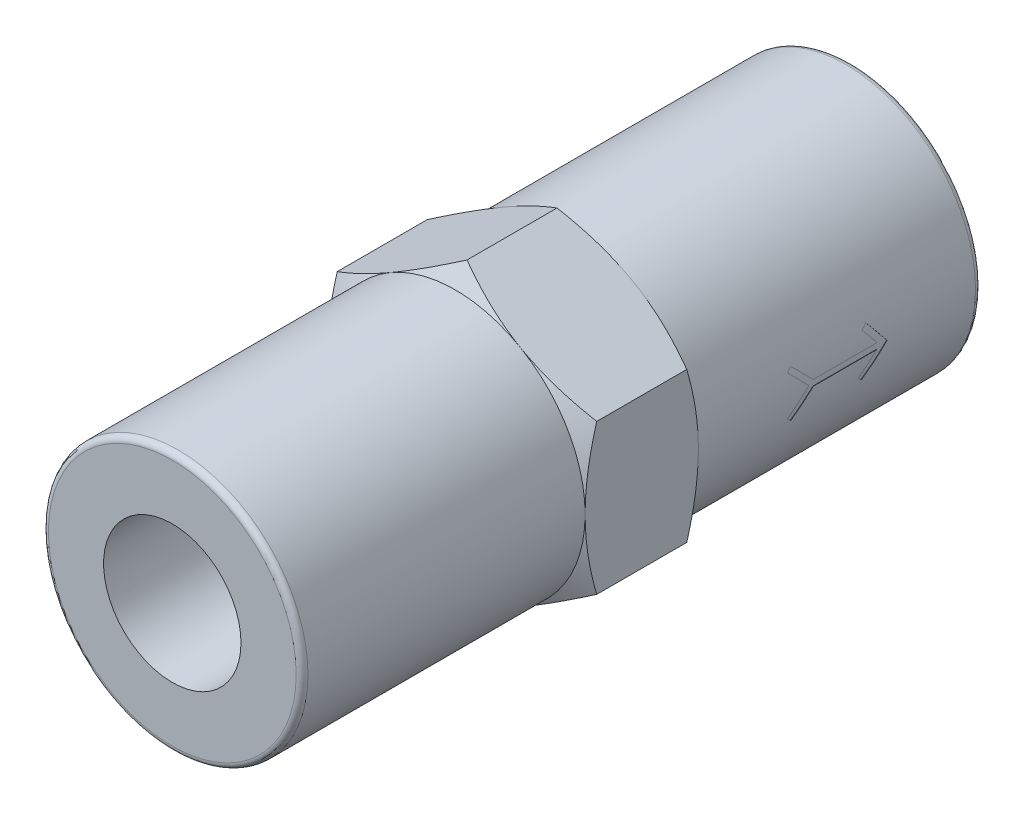
SolidWorks part; units mm, degrees
ref_plane "Front Plane" through (0, 0, 0) normal (0, 0, 1) x (1, 0, 0)
ref_plane "Top Plane" through (0, 0, 0) normal (0, 1, 0) x (1, 0, 0)
ref_plane "Right Plane" through (0, 0, 0) normal (1, 0, 0) x (0, 0, -1)
sketch "Sketch1" plane through (0, 0, 0) normal (1, 0, 0) x (0, 0, -1)
  line L0 (-22.86, 0) -> (22.86, 0) construction
  line L1 (-3.81, 0) -> (3.81, 0) construction
  line L2 (0, 8.7312) -> (0, -8.7312) construction
  line L3 (-22.86, 6.858) -> (-22.86, -6.858) construction
  line L4 (-22.86, 6.858) -> (-12.6543, 6.5402) construction
  line L5 (-12.6543, 6.5402) -> (-12.6543, 0) construction
  line L6 (22.86, 6.858) -> (22.86, -6.858) construction
  line L7 (22.86, 6.858) -> (12.6543, 6.5402) construction
  line L8 (12.6543, 6.5402) -> (12.6543, 0) construction
  line L9 (0, 4.6228) -> (0, -4.6228) construction
  point P17 (-22.86, 8.7312)
  point P18 (22.86, 8.7312)
  dimension "A1" = 1.783
  dimension "A2" = 1.783
sketch "Sketch1.1" plane through (0, 0, 0) normal (0, 0, 1) x (1, 0, 0)
  line L1 (0, 10.082) -> (-8.7312, 5.041)
  line L2 (-8.7312, 5.041) -> (-8.7313, -5.041)
  line L3 (-8.7313, -5.041) -> (0, -10.082)
  line L4 (0, -10.082) -> (8.7312, -5.041)
  line L5 (8.7312, -5.041) -> (8.7312, 5.041)
  line L6 (8.7312, 5.041) -> (0, 10.082)
  circle A0 centre (0, 0) radius 8.7312 construction
extrude "Extrude1" add sketch "Sketch1.1" along normal up to vertex (22.86 mm away) and the other way up to vertex (22.86 mm away) up to point (0, 0, 22.86) other way up to point (0, 0, -22.86)
ref_axis "Axis1" through (0, 0, -31.4325) along (0, 0, 1)
sketch "Sketch2.0" [suppressed] plane through (0, 0, 0) normal (0, 0, 1) x (1, 0, 0)
  circle A0 centre (0, 0) radius 12.7 construction
  circle A1 centre (0, 0) radius 12.7
extrude "Extrude2.0" [suppressed] cut sketch "Sketch2.0" along normal up to vertex and the other way up to vertex flip side to cut
sketch "Sketch2.1" [suppressed] plane through (0, 0, 32.385) normal (0, 0, 1) x (1, 0, 0)
  circle A0 centre (0, 0) radius 12.7 construction
  circle A1 centre (0, 0) radius 12.7
extrude "Extrude2.1" [suppressed] cut sketch "Sketch2.1" against normal through all draft 60 flip side to cut
sketch "Sketch2.2" [suppressed] plane through (0, 0, 6.985) normal (0, 0, -1) x (-1, 0, 0)
  circle A0 centre (0, 0) radius 12.7 construction
  circle A1 centre (0, 0) radius 12.7
extrude "Extrude2.2" [suppressed] cut sketch "Sketch2.2" against normal through all draft 60 flip side to cut
sketch "Sketch2.3" [suppressed] plane through (0, 0, -6.985) normal (0, 0, 1) x (1, 0, 0)
  circle A0 centre (0, 0) radius 12.7 construction
  circle A1 centre (0, 0) radius 12.7
extrude "Extrude2.3" [suppressed] cut sketch "Sketch2.3" against normal through all draft 60 flip side to cut
sketch "Sketch2.4" [suppressed] plane through (0, 0, -32.385) normal (0, 0, -1) x (-1, 0, 0)
  circle A0 centre (0, 0) radius 12.7 construction
  circle A1 centre (0, 0) radius 12.7
extrude "Extrude2.4" [suppressed] cut sketch "Sketch2.4" against normal through all draft 60 flip side to cut
sketch "Sketch2.5" [suppressed] plane through (0, 0, 0) normal (1, 0, 0) x (0, 0, -1)
  line L0 (-3.8678, 0) -> (5.715, 0) construction
  line L1 (5.715, 0) -> (2.8575, 2.8575)
  line L2 (-3.8678, 0) -> (-5.715, 0) construction
  line L3 (-5.715, 2.8575) -> (-3.2147, 0.3572)
  line L4 (-5.715, 2.8575) -> (-5.715, -2.8575) construction
  line L5 (2.8575, -2.8575) -> (5.715, 0)
  line L6 (-3.2147, -0.3572) -> (-5.715, -2.8575)
  line L7 (-5.715, -2.8575) -> (2.8575, -2.8575) construction
  line L8 (2.8575, -2.8575) -> (2.8575, 2.8575) construction
  line L9 (2.8575, 2.8575) -> (-5.715, 2.8575) construction
  line L10 (-6.985, 0) -> (-5.715, 0) construction
  line L12 (5.715, 0) -> (6.985, 0) construction
  line L14 (-5.715, 2.8575) -> (-6.2201, 2.3524)
  line L15 (-6.2201, 2.3524) -> (-3.8678, 0)
  line L16 (-5.715, -2.8575) -> (-6.2201, -2.3524)
  line L17 (-6.2201, -2.3524) -> (-3.8678, 0)
  line L18 (-3.2147, 0.3572) -> (4.3475, 0.3572)
  line L19 (-6.2201, 2.3524) -> (2.3524, 2.3524) construction
  line L20 (4.3475, -0.3572) -> (-3.2147, -0.3572)
  line L21 (2.8575, 2.8575) -> (2.3524, 2.3524)
  line L22 (2.3524, 2.3524) -> (4.3475, 0.3572)
  line L23 (-6.2201, -2.3524) -> (2.3524, -2.3524) construction
  line L24 (2.8575, -2.8575) -> (2.3524, -2.3524)
  line L25 (2.3524, -2.3524) -> (4.3475, -0.3572)
  line L26 (0.5664, 0.3572) -> (0.5664, -0.3572) construction
  line L27 (0.5664, 0) -> (0, 0) construction
  dimension "D1" = 0.7144
  dimension "D2" = 5.715
  dimension "D3" = 11.43
  dimension "D4" = 1.27
extrude "Extrude2.5" [suppressed] cut sketch "Sketch2.5" against normal blind 0.0254 from surface
pattern_circular "CirPattern1" [suppressed] count 2 over 360 about axis through (0, 0, -31.4325) along (0, 0, 1) of bodies 117
sketch "Sketch3.1" plane through (0, 0, 0) normal (0, 0, 1) x (1, 0, 0)
  circle A0 centre (0, 0) radius 8.7312
extrude "Extrude3.0" cut sketch "Sketch3.1" along normal up to vertex (22.86 mm away) from vertex flip side to cut up to point (0, 0, 22.86) starting at point (0, 0, 3.81)
extrude "Extrude3.1" cut sketch "Sketch3.1<2>" against normal up to vertex (22.86 mm away) from vertex flip side to cut up to point (0, 0, -22.86) starting at point (0, 0, -3.81)
sketch "Sketch3.1<2>" plane through (0, 0, 0) normal (0, 0, 1) x (1, 0, 0) same geometry as "Sketch3.1"
sketch "Sketch3.2" plane through (0, 0, 3.81) normal (0, 0, 1) x (1, 0, 0)
  circle A0 centre (0, 0) radius 8.7312 construction
  circle A1 centre (0, 0) radius 8.7312
extrude "Extrude3.2" cut sketch "Sketch3.2" against normal through all draft 60 flip side to cut
sketch "Sketch3.3" plane through (0, 0, -3.81) normal (0, 0, -1) x (-1, 0, 0)
  circle A0 centre (0, 0) radius 8.7312 construction
  circle A1 centre (0, 0) radius 8.7312
extrude "Extrude3.3" cut sketch "Sketch3.3" against normal through all draft 60 flip side to cut
fillet "Fillet1" radius 0.3969 2 edges at (8.7312, 0, -22.86) (8.7312, 0, 22.86)
sketch "Sketch3.4" plane through (0, 0, 0) normal (1, 0, 0) x (0, 0, -1)
  line L0 (10.16, 0) -> (16.51, 0) construction
  line L1 (3.81, 0) -> (10.16, 0) construction
  line L2 (16.51, 0) -> (22.86, 0) construction
  line L3 (22.86, -8.3344) -> (22.86, 8.3344) construction
  line L4 (10.16, 1.5875) -> (10.16, -1.5875) construction
  line L5 (10.16, -1.5875) -> (16.51, -1.5875) construction
  line L6 (16.51, -1.5875) -> (16.51, 1.5875) construction
  line L7 (16.51, 1.5875) -> (10.16, 1.5875) construction
  line L8 (10.16, 1.5875) -> (11.5491, 0.1984)
  line L9 (11.5491, -0.1984) -> (10.16, -1.5875)
  line L10 (10.16, -1.5875) -> (9.9111, -1.3386)
  line L11 (9.9111, -1.3386) -> (11.2497, 0)
  line L12 (11.2497, 0) -> (9.9111, 1.3386)
  line L13 (9.9111, 1.3386) -> (10.16, 1.5875)
  line L14 (15.2316, 1.5875) -> (14.9225, 1.3386)
  line L15 (14.9225, 1.3386) -> (9.9111, 1.3386) construction
  line L16 (9.9111, 1.3386) -> (9.9111, -1.3386) construction
  line L17 (9.9111, -1.3386) -> (14.6736, -1.3386) construction
  line L18 (14.9225, -1.5875) -> (14.9225, 1.3386) construction
  line L19 (14.9225, 1.3386) -> (15.8406, 0.1984)
  line L20 (15.2316, 1.5875) -> (16.51, 0)
  line L21 (16.51, 0) -> (14.9225, -1.5875)
  line L22 (14.9225, -1.5875) -> (14.6736, -1.3386)
  line L23 (14.6736, -1.3386) -> (15.8137, -0.1984)
  line L24 (11.5491, 0.1984) -> (15.8406, 0.1984)
  line L25 (11.5491, -0.1984) -> (15.8137, -0.1984)
  line L28 (13.335, -0.1984) -> (13.335, 0.1984) construction
  point P28 (13.335, 0)
  dimension "D2" = 0.3969
  dimension "D3" = 3.175
  dimension "D1" = 6.35
extrude "Extrude3.4" cut sketch "Sketch3.4" against normal blind 0.0254 from surface starting at face at (8.7312, 0, -22.4631)
pattern_circular "CirPattern3" count 2 over 360 about axis through (0, 0, -31.4325) along (0, 0, 1) of "Extrude3.4"
sketch "Sketch4" plane through (0, 0, 0) normal (0, 0, 1) x (1, 0, 0)
  circle A0 centre (0, 0) radius 4.6228
extrude "Extrude4" cut sketch "Sketch4" against normal through all and the other way through all
sketch "Sketch5" plane through (0, 0, 0) normal (0, 0, 1) x (1, 0, 0)
  circle A1 centre (0, 0) radius 4.6228 construction
  circle A2 centre (0, 0) radius 4.6228
extrude "Extrude5" add sketch "Sketch5" along normal up to vertex (3.81 mm away) and the other way up to vertex (3.81 mm away) up to point (0, 0, 3.81) other way up to point (0, 0, -3.81)
sketch "Sketch7" [suppressed] plane through (0, 0, 22.86) normal (0, 0, 1) x (1, 0, 0)
  circle A0 centre (0, 0) radius 6.858
extrude "Extrude7" [suppressed] cut sketch "Sketch7" against normal up to vertex draft 1.783
sketch "Sketch8" [suppressed] plane through (0, 0, 12.6543) normal (0, 0, 1) x (1, 0, 0)
  circle A0 centre (0, 0) radius 6.5402 construction
  circle A1 centre (0, 0) radius 6.5402
curve "Helix/Spiral1" [suppressed] parameters "Pitch 1"=1.4111
sketch "Sketch9" [suppressed] plane through (0, 0, 0) normal (1, 0, 0) x (0, 0, -1)
  line L0 (-12.0369, 6.5402) -> (-12.0369, 5.6237) construction
  line L1 (-12.7425, 6.693) -> (-11.3314, 6.693) construction
  line L2 (-11.3314, 6.693) -> (-12.0369, 5.4709) construction
  line L3 (-12.0369, 5.4709) -> (-12.7425, 6.693) construction
  line L4 (-12.6543, 6.5402) -> (-11.4196, 6.5402) construction
  line L5 (-12.0369, 6.5402) -> (-12.0369, 6.693) construction
  line L6 (-12.0369, 5.6237) -> (-12.0369, 5.4709) construction
  line L7 (-11.4196, 6.5402) -> (-11.9487, 5.6237)
  line L8 (-11.9487, 5.6237) -> (-12.1251, 5.6237)
  line L9 (-12.1251, 5.6237) -> (-12.7425, 6.693)
  line L12 (-12.7425, 6.693) -> (-11.4196, 6.5402)
  dimension "D1" = 0.1764
sweep "Sweep1" [suppressed] add profiles "Sketch9" path "Helix/Spiral1"
sketch "Sketch10" [suppressed] plane through (0, 0, 22.86) normal (0, 0, 1) x (1, 0, 0)
  circle A0 centre (0, 0) radius 6.858 construction
  circle A1 centre (0, 0) radius 6.858 construction
  circle A2 centre (0, 0) radius 7.2108
  dimension "D1" = 0.3528
extrude "Extrude8" [suppressed] cut sketch "Sketch10" against normal through all draft 45 and the other way through all draft 45
sketch "Sketch11" [suppressed] plane through (0, 0, -22.86) normal (0, 0, -1) x (-1, 0, 0)
  circle A0 centre (0, 0) radius 6.858
extrude "Extrude9" [suppressed] cut sketch "Sketch11" against normal up to vertex draft 1.783
sketch "Sketch12" [suppressed] plane through (0, 0, -12.6543) normal (0, 0, -1) x (-1, 0, 0)
  circle A0 centre (0, 0) radius 6.5402 construction
  circle A1 centre (0, 0) radius 6.5402
curve "Helix/Spiral2" [suppressed] parameters "Pitch 2"=1.4111
sketch "Sketch13" [suppressed] plane through (0, 0, 0) normal (1, 0, 0) x (0, 0, -1)
  line L0 (11.3314, 6.693) -> (12.0369, 5.4709) construction
  line L1 (12.0369, 5.4709) -> (12.7425, 6.693) construction
  line L2 (12.7425, 6.693) -> (11.3314, 6.693) construction
  line L3 (12.0369, 6.5402) -> (12.0369, 5.6237) construction
  line L4 (11.4196, 6.5402) -> (12.6543, 6.5402) construction
  line L5 (12.0369, 6.5402) -> (12.0369, 6.693) construction
  line L6 (11.9487, 5.6237) -> (11.4196, 6.5402)
  line L7 (11.4196, 6.5402) -> (12.7425, 6.693)
  line L8 (11.9487, 5.6237) -> (12.1251, 5.6237)
  line L9 (12.7425, 6.693) -> (12.1251, 5.6237)
  line L10 (12.0369, 5.6237) -> (12.0369, 5.4709) construction
  dimension "D1" = 0.1764
  dimension "A1" = 60
sweep "Sweep2" [suppressed] add profiles "Sketch13" path "Helix/Spiral2"
sketch "Sketch14" [suppressed] plane through (0, 0, -22.86) normal (0, 0, -1) x (-1, 0, 0)
  circle A0 centre (0, 0) radius 6.858 construction
  circle A1 centre (0, 0) radius 6.858 construction
  circle A2 centre (0, 0) radius 7.2108
  dimension "D1" = 0.3528
extrude "Extrude10" [suppressed] cut sketch "Sketch14" against normal through all draft 45 and the other way through all draft 45
equation "\"D6@Helix/Spiral1\" = \"A1@Sketch1\""
equation "\"D3@Helix/Spiral1\" = \"Thread Lenght 1@Sketch1\" + \"Pitch 1@Helix/Spiral1\""
equation "\"Pitch 1@Sketch9\" = \"Pitch 1@Helix/Spiral1\""
equation "\"D1@Sketch9\" = \"Pitch 1@Sketch9\" * 1 / 8"
equation "\"D1@Sketch10\" = \"Pitch 1@Helix/Spiral1\" * 1 / 4"
equation "\"D6@Helix/Spiral2\" = \"A2@Sketch1\""
equation "\"D3@Helix/Spiral2\" = \"Thread Lenght 2@Sketch1\" + \"Pitch 2@Helix/Spiral2\""
equation "\"Pitch 2@Sketch13\" = \"Pitch 2@Helix/Spiral2\""
equation "\"D1@Sketch13\" = \"Pitch 2@Sketch13\" * 1 / 8"
equation "\"D1@Sketch14\" = \"Pitch 2@Helix/Spiral2\" * 1 / 4"
equation "\"D2@Sketch2.5\" = \"D3@Sketch2.5\" * 1 / 2"
equation "\"D1@Sketch2.5\" = \"D2@Sketch2.5\" * 1 / 8"
equation "\"D3@Sketch3.4\" = \"D1@Sketch3.4\" * 1 / 2"
equation "\"D2@Sketch3.4\" = \"D3@Sketch3.4\" * 1 / 8"
